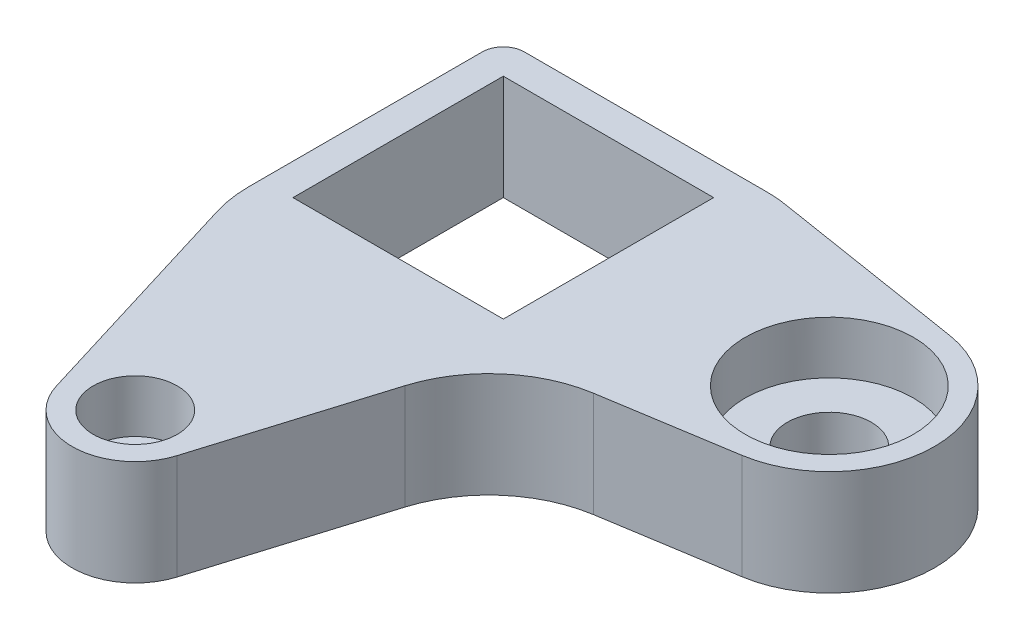
SolidWorks part; units mm, degrees
ref_plane "Front Plane" through (0, 0, 0) normal (0, 0, 1) x (1, 0, 0)
ref_plane "Top Plane" through (0, 0, 0) normal (0, 1, 0) x (1, 0, 0)
ref_plane "Right Plane" through (0, 0, 0) normal (1, 0, 0) x (0, 0, -1)
sketch "Sketch1" plane through (0, 0, 0) normal (0, 1, 0) x (1, 0, 0)
  line L0 (20, 0) -> (41, -10) construction
  line L1 (10, -45) -> (0, -20) construction
  line L2 (41, -10) -> (20, -20) construction
  line L3 (0, 0) -> (0, -20) construction
  line L4 (0, 0) -> (20, -20) construction
  line L5 (23.9399, 2.85) -> (42.5764, -0.125)
  line L12 (-3, -23) -> (23, -23) construction
  line L13 (0, 0) -> (20, 0) construction
  line L14 (0, 0) -> (0, -20) construction
  line L15 (0, -20) -> (20, -20) construction
  line L16 (20, 0) -> (20, -20) construction
  line L17 (10, -45) -> (20, -20) construction
  line L18 (-3, -21.2066) -> (-3, 1)
  line L19 (-1, 3) -> (22.0482, 3)
  line L20 (23, -23) -> (23, 3) construction
  line L21 (-3, -23) -> (23, 3) construction
  line L22 (-3, 3) -> (23, -23) construction
  line L23 (0, -20) -> (20, -20)
  line L24 (0, -20) -> (0, 0)
  line L25 (0, 0) -> (20, 0)
  line L26 (20, -20) -> (20, 0)
  line L27 (0, -20) -> (20, 0) construction
  line L28 (0, 0) -> (20, -20) construction
  line L29 (30.3947, -21.8196) -> (42.5764, -19.875)
  line L30 (20.8107, -30.1612) -> (15.7378, -46.7542)
  line L31 (-2.4757, -24.715) -> (4.2622, -46.7542)
  circle A4 centre (10, -45) radius 4 construction
  circle A5 centre (41, -10) radius 4 construction
  arc A6 (-3, 1) -> (-1, 3) centre (-1, 1) cw
  circle A7 centre (41, -10) radius 8 construction
  arc A8 (42.5764, -19.875) -> (42.5764, -0.125) centre (41, -10) ccw
  arc A9 (4.2622, -46.7542) -> (15.7378, -46.7542) centre (10, -45) ccw
  arc A10 (30.3947, -21.8196) -> (20.8107, -30.1612) centre (32.2864, -33.6695) ccw
  arc A11 (23.9399, 2.85) -> (22.0482, 3) centre (22.0482, -9) ccw
  arc A12 (-3, -21.2066) -> (-2.4757, -24.715) centre (9, -21.2066) ccw
  point P0 (10, -10)
  point P10 (10, -10)
  dimension "D6" = 8
  dimension "D7" = 16
  dimension "D8" = 20
  dimension "D9" = 12
  dimension "D10" = 12
  dimension "D11" = 12
  dimension "D5" = 2
  dimension "D2" = 20
  dimension "D3" = 3
  dimension "D4" = 45
  dimension "D12" = 20
  dimension "D13" = 41
extrude "Boss-Extrude1" add sketch "Sketch1" along normal blind 10
ref_plane "Plane1" through (0, 5, 0) normal (0, 1, 0) x (1, 0, 0)
sketch "Sketch2" plane through (0, 5, 0) normal (0, 1, 0) x (1, 0, 0)
  line L0 (20, 0) -> (41, -10) construction
  line L1 (10, -45) -> (0, -20) construction
  line L2 (41, -10) -> (20, -20) construction
  line L3 (0, 0) -> (0, -20) construction
  line L4 (0, 0) -> (20, -20) construction
  line L5 (23.9399, 2.85) -> (42.5764, -0.125) construction
  line L6 (-3, -23) -> (23, -23) construction
  line L7 (0, 0) -> (20, 0) construction
  line L8 (0, 0) -> (0, -20) construction
  line L9 (0, -20) -> (20, -20) construction
  line L10 (20, 0) -> (20, -20) construction
  line L11 (10, -45) -> (20, -20) construction
  line L12 (-3, -21.2066) -> (-3, 1) construction
  line L13 (-1, 3) -> (22.0482, 3) construction
  line L14 (23, -23) -> (23, 3) construction
  line L15 (-3, -23) -> (23, 3) construction
  line L16 (-3, 3) -> (23, -23) construction
  line L17 (0, -20) -> (20, -20) construction
  line L18 (0, -20) -> (0, 0) construction
  line L19 (0, 0) -> (20, 0) construction
  line L20 (20, -20) -> (20, 0) construction
  line L21 (0, -20) -> (20, 0) construction
  line L22 (0, 0) -> (20, -20) construction
  line L23 (30.3947, -21.8196) -> (42.5764, -19.875) construction
  line L24 (20.8107, -30.1612) -> (15.7378, -46.7542) construction
  line L25 (-2.4757, -24.715) -> (4.2622, -46.7542) construction
  circle A0 centre (10, -45) radius 4
  circle A1 centre (41, -10) radius 4 construction
  arc A2 (-3, 1) -> (-1, 3) centre (-1, 1) cw construction
  circle A3 centre (41, -10) radius 8
  arc A4 (42.5764, -19.875) -> (42.5764, -0.125) centre (41, -10) ccw construction
  arc A5 (4.2622, -46.7542) -> (15.7378, -46.7542) centre (10, -45) ccw construction
  arc A6 (30.3947, -21.8196) -> (20.8107, -30.1612) centre (32.2864, -33.6695) ccw construction
  arc A7 (23.9399, 2.85) -> (22.0482, 3) centre (22.0482, -9) ccw construction
  arc A8 (-3, -21.2066) -> (-2.4757, -24.715) centre (9, -21.2066) ccw construction
  point P0 (10, -10)
  point P10 (10, -10)
  dimension "D2" = 8
  dimension "D7" = 2
  dimension "D8" = 16
  dimension "D9" = 20
  dimension "D10" = 12
  dimension "D11" = 12
  dimension "D12" = 12
  dimension "D1" = 20
  dimension "D3" = 20
  dimension "D4" = 41
  dimension "D5" = 45
  dimension "D6" = 3
sketch "Sketch3" plane through (0, 5, -5) normal (0, -1, 0) x (1, 0, 0)
  line L13 (-1, 2) -> (22.0482, 2) construction
  line L27 (-1, 2) -> (22.0482, 2) construction
  line L28 (-2.4757, 29.715) -> (4.2622, 51.7542) construction
  line L29 (20.8107, 35.1612) -> (15.7378, 51.7542) construction
  line L30 (30.3947, 26.8196) -> (42.5764, 24.875) construction
  line L31 (0, 5) -> (20, 25) construction
  line L32 (0, 25) -> (20, 5) construction
  line L33 (20, 25) -> (20, 5) construction
  line L34 (0, 5) -> (20, 5) construction
  line L35 (0, 25) -> (0, 5) construction
  line L36 (0, 25) -> (20, 25) construction
  line L37 (-3, 2) -> (23, 28) construction
  line L38 (-3, 28) -> (23, 2) construction
  line L39 (23, 28) -> (23, 2) construction
  line L40 (-3, 26.2066) -> (-3, 4) construction
  line L41 (10, 50) -> (20, 25) construction
  line L42 (20, 5) -> (20, 25) construction
  line L43 (0, 25) -> (20, 25) construction
  line L44 (0, 5) -> (0, 25) construction
  line L45 (0, 5) -> (20, 5) construction
  line L46 (-3, 28) -> (23, 28) construction
  line L47 (23.9399, 2.15) -> (42.5764, 5.125) construction
  line L48 (0, 5) -> (20, 25) construction
  line L49 (0, 5) -> (0, 25) construction
  line L50 (41, 15) -> (20, 25) construction
  line L51 (10, 50) -> (0, 25) construction
  line L52 (20, 5) -> (41, 15) construction
  arc A9 (-3, 26.2066) -> (-2.4757, 29.715) centre (9, 26.2066) cw construction
  arc A10 (23.9399, 2.15) -> (22.0482, 2) centre (22.0482, 14) cw construction
  arc A11 (30.3947, 26.8196) -> (20.8107, 35.1612) centre (32.2864, 38.6695) cw construction
  arc A12 (4.2622, 51.7542) -> (15.7378, 51.7542) centre (10, 50) cw construction
  arc A13 (42.5764, 24.875) -> (42.5764, 5.125) centre (41, 15) cw construction
  arc A14 (-3, 4) -> (-1, 2) centre (-1, 4) ccw construction
  circle A15 centre (41, 15) radius 4
  circle A16 centre (41, 15) radius 8 construction
  circle A17 centre (10, 50) radius 4 construction
  point P112 (10, 15)
  point P113 (10, 15)
extrude "Cut-Extrude2" cut sketch "Sketch2" along normal blind 46
extrude "Cut-Extrude4" cut sketch "Sketch3" along normal blind 36
